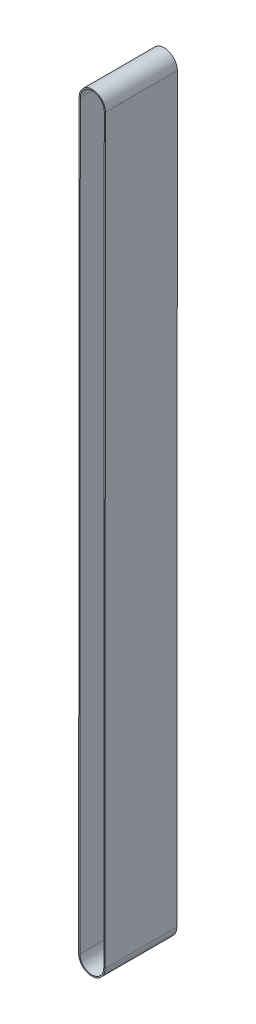
SolidWorks part; units mm, degrees
ref_plane "Front Plane" through (0, 0, 0) normal (0, 0, 1) x (1, 0, 0)
ref_plane "Top Plane" through (0, 0, 0) normal (0, 1, 0) x (1, 0, 0)
ref_plane "Right Plane" through (0, 0, 0) normal (1, 0, 0) x (0, 0, -1)
sketch "Sketch1" plane through (0, 0, 0) normal (0, 0, 1) x (1, 0, 0)
  line L0 (-96, 3110.0156) -> (-100, -3080)
  line L1 (100, -3080) -> (104, 3110.0156)
  circle A0 centre (4, 3110.0156) radius 100 construction
  arc A1 (103.9999, 3109.8864) -> (-96, 3110.0156) centre (4, 3110.0156) ccw
  circle A2 centre (0, -3080) radius 100 construction
  arc A3 (-99.9999, -3079.8708) -> (100, -3080) centre (0, -3080) ccw
extrude "Extrude-Thin3" add sketch "Sketch1" along normal mid plane 600 thin thin type one direction wall 10
